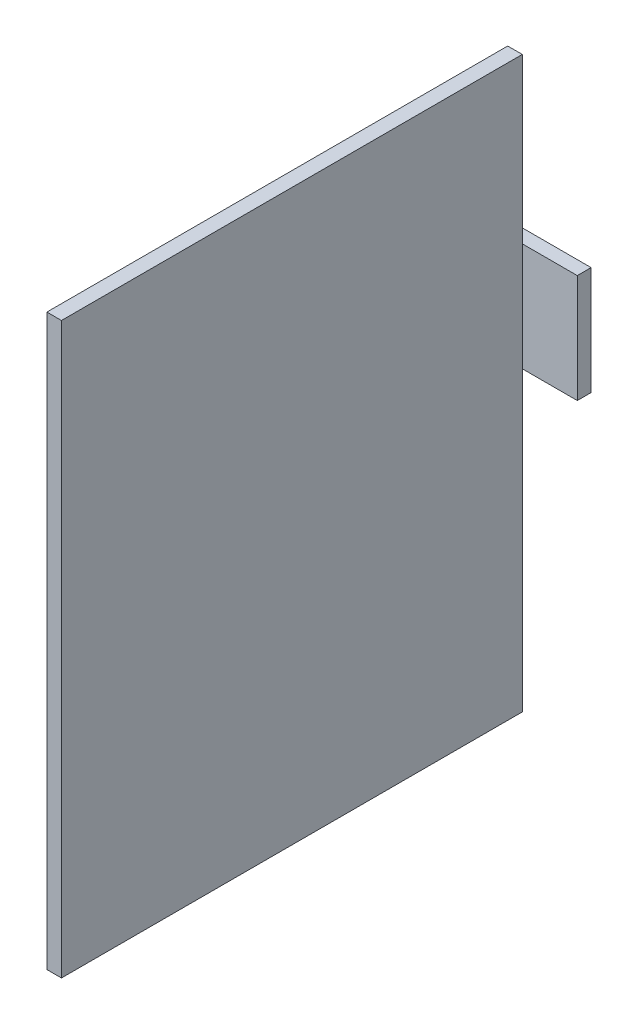
SolidWorks part; units mm, degrees
ref_plane "前视基准面" through (0, 0, 0) normal (0, 0, 1) x (1, 0, 0)
ref_plane "上视基准面" through (0, 0, 0) normal (0, 1, 0) x (1, 0, 0)
ref_plane "右视基准面" through (0, 0, 0) normal (1, 0, 0) x (0, 0, -1)
other "Configuration Table"
sketch "草图2" plane through (0, 0, 0) normal (0, 0, 1) x (1, 0, 0)
  line L1 (-33.5891, 12.169) -> (-9.8867, 12.169)
  line L2 (-33.5891, 12.169) -> (-33.5891, -11.3205)
  line L3 (-33.5891, -11.3205) -> (-9.8867, -11.3205)
  line L4 (-9.8867, 12.169) -> (-9.8867, -11.3205)
  point P5 (-33.5891, 12.169)
extrude "凸台-拉伸1" add sketch "草图2" along normal blind 3
sketch "草图3" plane through (0, 0, 3) normal (0, 0, 1) x (1, 0, 0)
  line L1 (-21.8225, 47.762) -> (-24.988, 47.762)
  line L2 (-21.8225, 47.762) -> (-21.8225, -75.806)
  line L3 (-21.8225, -75.806) -> (-24.988, -75.806)
  line L4 (-24.988, 47.762) -> (-24.988, -75.806)
  point P5 (-21.8225, -62.0523)
  point P6 (-21.8225, -75.806)
extrude "凸台-拉伸2" add sketch "草图3" along normal blind 100
fillet "圆角1" radius 30 1 edges at (-24.988, 0.4243, 3)
